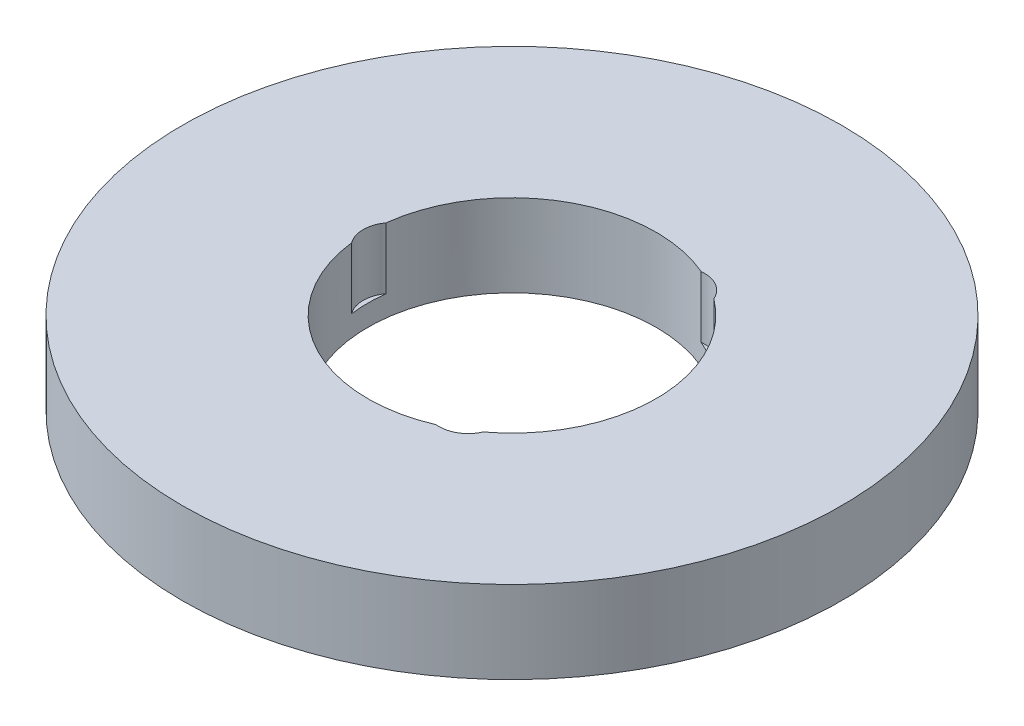
SolidWorks part; units mm, degrees
ref_plane "Front Plane" through (0, 0, 0) normal (0, 0, 1) x (1, 0, 0)
ref_plane "Top Plane" through (0, 0, 0) normal (0, 1, 0) x (1, 0, 0)
ref_plane "Right Plane" through (0, 0, 0) normal (1, 0, 0) x (0, 0, -1)
sketch "Sketch1" plane through (0, 0, 0) normal (0, 1, 0) x (1, 0, 0)
  circle A0 centre (0, 0) radius 40
  dimension "FLANGE_OD" = 80
extrude "Boss-Extrude1" add sketch "Sketch1" along normal blind 10
sketch "Sketch2" plane through (0, 0, 0) normal (0, 1, 0) x (1, 0, 0)
  circle A0 centre (0, 0) radius 17.5
  dimension "BORE_D" = 35
extrude "Cut-Extrude1" cut sketch "Sketch2" along normal through all
sketch "Sketch3" plane through (0, 10, 0) normal (0, 1, 0) x (1, 0, 0)
  circle A0 centre (0, 0) radius 14.5284 construction
  circle A1 centre (-14.5284, 0) radius 3.531
  dimension "BOLT_D" = 7.0621
  dimension "BOLT_PCD" = 29.0569
extrude "Cut-Extrude2" cut sketch "Sketch3" against normal blind 7.446
pattern_circular "CirPattern1" count 3 over 360 about axis through (0, 0, 0) along (0, 1, 0) of "Cut-Extrude2"
